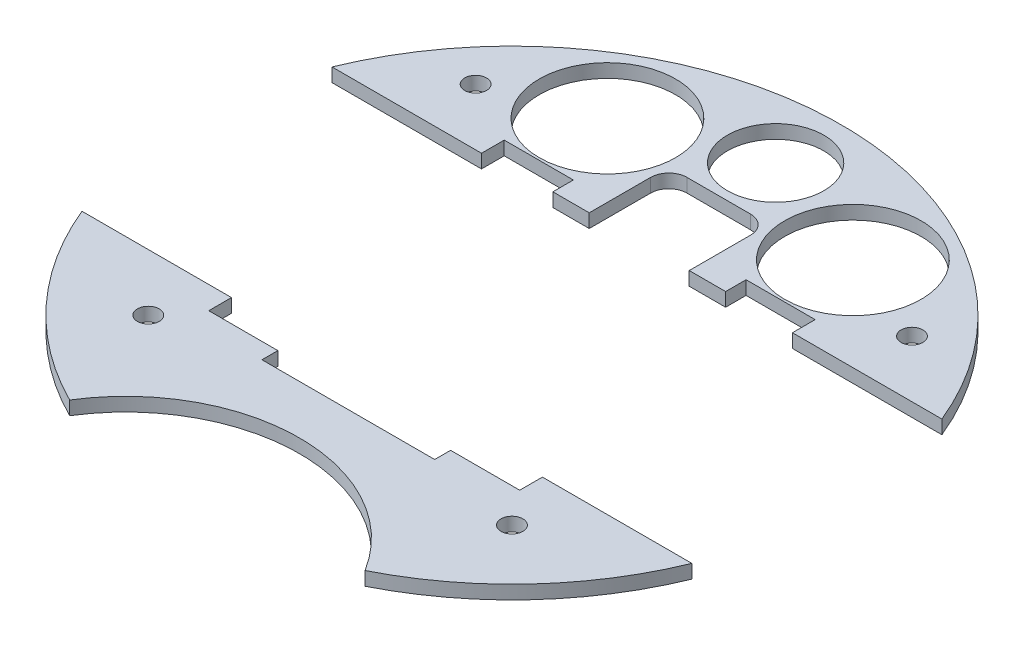
SolidWorks part; units mm, degrees
material "ABS"
ref_plane "Front Plane" through (0, 0, 0) normal (0, 0, 1) x (1, 0, 0)
ref_plane "Top Plane" through (0, 0, 0) normal (0, 1, 0) x (1, 0, 0)
ref_plane "Right Plane" through (0, 0, 0) normal (1, 0, 0) x (0, 0, -1)
sketch "Sketch1" plane through (0, 0, 0) normal (0, 1, 0) x (1, 0, 0)
  line L0 (0, -85) -> (-32.4891, -64.8129) construction
  line L1 (0, -85) -> (0, 0) construction
  arc A0 (32.4891, -64.8129) -> (-32.4891, -64.8129) centre (0, 0) ccw
  arc A1 (32.4891, -64.8129) -> (-32.4891, -64.8129) centre (0, -85) ccw
  dimension "D1" = 145
  dimension "D2" = 76.5
  dimension "D3" = 85
extrude "Boss-Extrude1" add sketch "Sketch1" along normal blind 3
sketch "solenoid placement" plane through (0, 3, 0) normal (0, 1, 0) x (1, 0, 0)
  line L4 (-19, -36) -> (19, -36)
  line L5 (-19, -36) -> (19, -36)
  line L6 (19, -36) -> (19, 28)
  line L7 (19, -36) -> (19, 28)
  line L8 (19, 28) -> (-19, 28)
  line L9 (19, 28) -> (-19, 28)
  line L10 (-19, 28) -> (-19, -36)
  line L11 (-19, 28) -> (-19, -36)
  circle A1 centre (0, 0) radius 72.5 construction
  arc A2 (32.4891, -64.8129) -> (-32.4891, -64.8129) centre (0, 0) ccw construction
  dimension "D1" = 0
extrude "Cut-Extrude1" cut sketch "solenoid placement" against normal through all
sketch "Sketch3" plane through (0, 3, 0) normal (0, 1, 0) x (1, 0, 0)
  circle A1 centre (27, 48) radius 12
  circle A2 centre (-27, 48) radius 12
  dimension "D1" = 24
extrude "Cut-Extrude3" cut sketch "Sketch3" against normal through all
sketch "Sketch4" plane through (0, 3, 0) normal (0, 1, 0) x (1, 0, 0)
  circle A2 centre (40, -40) radius 2.4
  circle A3 centre (40, -40) radius 2.4
  circle A4 centre (-40, -40) radius 2.4
  circle A5 centre (-40, -40) radius 2.4
  circle A6 centre (48, 40) radius 2.4
  circle A7 centre (48, 40) radius 2.4
  circle A8 centre (-48, 40) radius 2.4
  circle A12 centre (-48, 40) radius 2.4
  dimension "D1" = 0
  dimension "D2" = 0
  dimension "D3" = 0
  dimension "D4" = 0
extrude "Cut-Extrude4" cut sketch "Sketch4" against normal through all
sketch "Sketch2" plane through (0, 3, 0) normal (0, 1, 0) x (1, 0, 0)
  line L0 (0, 0) -> (0, 72.5) construction
  line L1 (34.2, -27.5) -> (34.2, -32.5)
  line L2 (67.082, -27.5) -> (34.2, -27.5)
  line L3 (34.2, 27.5) -> (67.082, 27.5)
  line L4 (34.2, 32.5) -> (34.2, 27.5)
  line L5 (22.2, 32.5) -> (34.2, 32.5)
  line L6 (19, 32.5) -> (22.2, 32.5)
  line L7 (19, -32.5) -> (19, 32.5)
  line L8 (22.2, -32.5) -> (19, -32.5)
  line L9 (-34.2, -32.5) -> (-22.2, -32.5)
  line L10 (-22.2, -32.5) -> (-19, -32.5)
  line L11 (-19, -32.5) -> (-19, 32.5)
  line L12 (-19, 32.5) -> (-22.2, 32.5)
  line L13 (-22.2, 32.5) -> (-34.2, 32.5)
  line L14 (-34.2, 32.5) -> (-34.2, 25)
  line L15 (-34.2, 25) -> (-68.0533, 25)
  line L16 (-68.0533, -25) -> (-34.2, -25)
  line L17 (-34.2, -25) -> (-34.2, -32.5)
  line L18 (-34.2, -32.5) -> (-22.2, -32.5)
  line L19 (-22.2, -32.5) -> (-19, -32.5)
  line L20 (-19, -32.5) -> (-19, 32.5)
  line L21 (-19, 32.5) -> (-22.2, 32.5)
  line L22 (-22.2, 32.5) -> (-34.2, 32.5)
  line L23 (-34.2, 32.5) -> (-34.2, 27.5)
  line L24 (-34.2, 27.5) -> (-67.082, 27.5)
  line L25 (-67.082, -27.5) -> (-34.2, -27.5)
  line L26 (-34.2, -27.5) -> (-34.2, -32.5)
  line L27 (34.2, -32.5) -> (22.2, -32.5)
  arc A0 (32.4891, -64.8129) -> (-32.4891, -64.8129) centre (0, 0) ccw construction
  arc A1 (67.082, 27.5) -> (67.082, -27.5) centre (0, 0) cw
  arc A2 (-68.0533, 25) -> (-68.0533, -25) centre (0, 0) ccw
  arc A3 (-67.082, 27.5) -> (-67.082, -27.5) centre (0, 0) ccw
  dimension "D2" = 55
  dimension "D1" = 0
extrude "Cut-Extrude2" cut sketch "Sketch2" against normal through all
sketch "Sketch5" plane through (0, 3, 0) normal (0, 1, 0) x (1, 0, 0)
  line L8 (-11, 28) -> (11, 28)
  line L9 (11, 28) -> (11, 41.5)
  line L10 (7, 45.5) -> (-7, 45.5)
  line L11 (-11, 41.5) -> (-11, 28)
  line L12 (19, 28) -> (-19, 28) construction
  arc A4 (11, 41.5) -> (7, 45.5) centre (7, 41.5) ccw
  arc A5 (-7, 45.5) -> (-11, 41.5) centre (-7, 41.5) ccw
  point P10 (0, 28)
  point P13 (0, 28)
  line M18 (-19, 28) -> (19, 28)
  dimension "D3" = 4
  dimension "D1" = 22
  dimension "D2" = 17.5
extrude "Cut-Extrude5" cut sketch "Sketch5" against normal through all contours L10 A5 L11 L9 A4 M18 region at (0, 3, -36.6073)
sketch "Sketch6" plane through (0, 3, 0) normal (0, 1, 0) x (-1, 0, 0)
  circle A1 centre (-27, -48) radius 15
  circle A2 centre (-27, -48) radius 15
  circle A3 centre (27, -48) radius 15
  circle A4 centre (27, -48) radius 15
  dimension "D1" = 0
  dimension "D2" = 0
extrude "Cut-Extrude10" cut sketch "Sketch6" against normal through all
sketch "Sketch7" plane through (0, 3, 0) normal (0, 1, 0) x (1, 0, 0)
  circle A1 centre (0, 58) radius 10.605
  circle A2 centre (0, 58) radius 10.605
  dimension "D1" = 0
extrude "Cut-Extrude11" cut sketch "Sketch7" against normal through all
equation "\"smallPulleyTeeth\"= 30"
equation "\"largePulleyTeeth\"= 30"
equation "\"eighthThick\"= 3.0mm"
equation "\"sixteenthThick\"= 1.7mm"
equation "\"quarterThick\"=6.0mm"
equation "\"OD\"= 145mm"
equation "\"puckAngle\"= 60.5deg"
equation "\"D1@Sketch1\"=\"OD\""
equation "\"puckDiam\"= 76.5mm"
equation "\"D2@Sketch1\"=\"puckDiam\""
equation "\"D1@Boss-Extrude1\"=\"eighthThick\""
equation "\"axlePress\"= 5.9mm"
equation "\"press\"= 0.2mm"
equation "\"wheelClear\"= 0.3mm"
equation "\"10-32clear\"= 4.8mm"
equation "\"6-32clear\"= 3.3mm"
equation "\"8-32clear\"= 4.0mm"
equation "\"wheelHeight\"= 22mm"
equation "\"wheelWell\"= 65mm"
equation "\"puckDist\"= 85mm"
equation "\"scoopFillet\"= 5mm"
equation "\"4-40clear\"= 3.0mm"
equation "\"D3@Sketch1\"=\"puckDist\""
